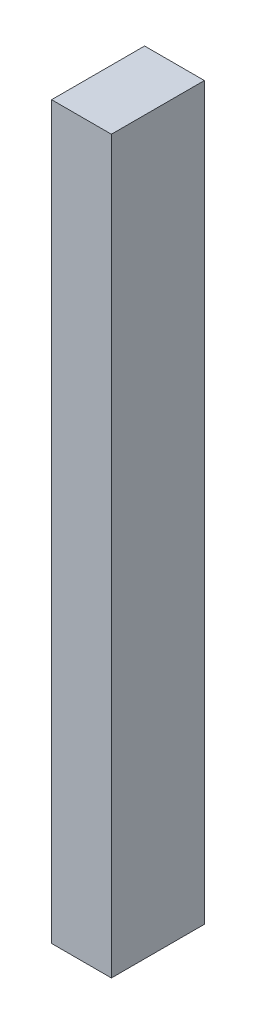
SolidWorks part; units mm, degrees
ref_plane "Alzado" through (0, 0, 0) normal (0, 0, 1) x (1, 0, 0)
ref_plane "Planta" through (0, 0, 0) normal (0, 1, 0) x (1, 0, 0)
ref_plane "Vista lateral" through (0, 0, 0) normal (1, 0, 0) x (0, 0, -1)
sketch "Croquis1" plane through (0, 0, 0) normal (0, 1, 0) x (1, 0, 0)
  line L0 (5.5287, 0) -> (-5.5287, 0) construction
  line L2 (3.15, 4.9) -> (-3.15, 4.9)
  line L3 (3.15, 4.9) -> (3.15, -4.9)
  line L4 (3.15, -4.9) -> (-3.15, -4.9)
  line L5 (-3.15, 4.9) -> (-3.15, -4.9)
  line L6 (3.15, 4.9) -> (-3.15, -4.9) construction
  line L7 (3.15, -4.9) -> (-3.15, 4.9) construction
  point P0 (0, 0)
  point P4 (0, 0)
  dimension "D1" = 6.3
  dimension "D2" = 9.8
extrude "Saliente-Extruir1" add sketch "Croquis1" along normal blind 77
